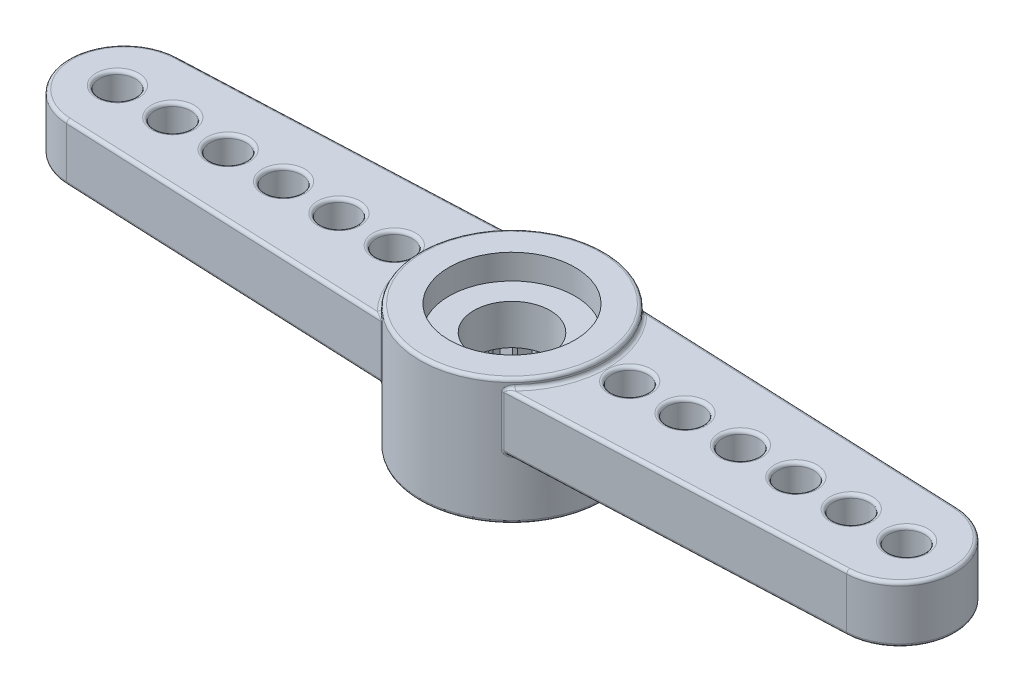
SolidWorks part; units mm, degrees
material "PETG"
ref_plane "Front Plane" through (0, 0, 0) normal (0, 0, 1) x (1, 0, 0)
ref_plane "Top Plane" through (0, 0, 0) normal (0, 1, 0) x (1, 0, 0)
ref_plane "Right Plane" through (0, 0, 0) normal (1, 0, 0) x (0, 0, -1)
ref_plane "Plane1" through (0, 2.35, 0) normal (0, 1, 0) x (1, 0, 0)
sketch "Sketch1" plane through (0, 2.35, 0) normal (0, 1, 0) x (1, 0, 0)
  line L0 (-2.1821, 2.5088) -> (-14.0857, 1.9982)
  line L1 (-14.0857, -1.9982) -> (-2.1821, -2.5088)
  arc A0 (-2.1821, -2.5088) -> (-2.1821, 2.5088) centre (0, 0) ccw
  arc A1 (-14.0857, 1.9982) -> (-14.0857, -1.9982) centre (-14, 0) ccw
extrude "Boss-Extrude1" add sketch "Sketch1" against normal blind 0.3
sketch "Sketch2" plane through (0, 2.05, 0) normal (0, -1, 0) x (1, 0, 0)
  line L0 (2.1821, 2.5088) -> (14.0857, 1.9982)
  line L1 (14.0857, -1.9982) -> (2.1821, -2.5088)
  line L2 (-2.1821, -2.5088) -> (-14.0857, -1.9982)
  line L3 (-14.0857, 1.9982) -> (-2.1821, 2.5088)
  arc A0 (14.0857, 1.9982) -> (14.0857, -1.9982) centre (14, 0) cw
  arc A1 (2.1821, -2.5088) -> (-2.1821, -2.5088) centre (0, 0) cw
  arc A2 (-14.0857, -1.9982) -> (-14.0857, 1.9982) centre (-14, 0) cw
  arc A3 (-2.1821, 2.5088) -> (2.1821, 2.5088) centre (0, 0) cw
extrude "Boss-Extrude2" add sketch "Sketch2" along normal blind 2.05
sketch "Sketch3" plane through (0, 2.35, 0) normal (0, 1, 0) x (-1, 0, 0)
  line L0 (14.0857, 1.9982) -> (2.1821, 2.5088)
  line L1 (2.1821, -2.5088) -> (14.0857, -1.9982)
  arc A0 (2.1821, 2.5088) -> (2.1821, -2.5088) centre (0, 0) cw
  arc A1 (14.0857, -1.9982) -> (14.0857, 1.9982) centre (14, 0) ccw
extrude "Cut-Extrude1" cut sketch "Sketch3" against normal blind 0.3
sketch "Sketch4" plane through (0, 0, 0) normal (0, -1, 0) x (1, 0, 0)
  circle A0 centre (0, 0) radius 3.325
extrude "Boss-Extrude3" add sketch "Sketch4" along normal blind 2.2
sketch "Sketch5" plane through (0, -2.2, 0) normal (0, -1, 0) x (1, 0, 0)
  line L0 (-2.15, -1.7146) -> (-1.4743, -1.4955)
  line L1 (-1.3811, -1.5819) -> (-1.5491, -2.2722)
  line L2 (-1.5491, -2.2722) -> (-0.968, -1.8636)
  line L3 (-0.8535, -1.9187) -> (-0.8106, -2.6278)
  line L4 (-0.8106, -2.6278) -> (-0.3757, -2.0661)
  line L5 (-0.25, -2.0851) -> (0, -2.75)
  line L6 (0, -2.75) -> (0.25, -2.0851)
  line L7 (0.3757, -2.0661) -> (0.8106, -2.6278)
  line L8 (0.8106, -2.6278) -> (0.8535, -1.9187)
  line L9 (0.968, -1.8636) -> (1.5491, -2.2722)
  line L10 (1.5491, -2.2722) -> (1.3811, -1.5819)
  line L11 (1.4743, -1.4955) -> (2.15, -1.7146)
  line L12 (2.15, -1.7146) -> (1.786, -1.1046)
  line L13 (1.8496, -0.9945) -> (2.5599, -1.0047)
  line L14 (2.5599, -1.0047) -> (2.0323, -0.529)
  line L15 (2.0606, -0.4051) -> (2.7423, -0.2055)
  line L16 (2.7423, -0.2055) -> (2.0979, 0.0935)
  line L17 (2.0884, 0.2202) -> (2.6811, 0.6119)
  line L18 (2.6811, 0.6119) -> (1.9772, 0.7077)
  line L19 (1.9307, 0.826) -> (2.3816, 1.375)
  line L20 (2.3816, 1.375) -> (1.6807, 1.259)
  line L21 (1.6015, 1.3584) -> (1.8705, 2.0159)
  line L22 (1.8705, 2.0159) -> (1.2349, 1.6985)
  line L23 (1.1299, 1.7701) -> (1.1932, 2.4777)
  line L24 (1.1932, 2.4777) -> (0.6794, 1.9871)
  line L25 (0.558, 2.0245) -> (0.4099, 2.7193)
  line L26 (0.4099, 2.7193) -> (0.0636, 2.099)
  line L27 (-0.0636, 2.099) -> (-0.4099, 2.7193)
  line L28 (-0.4099, 2.7193) -> (-0.558, 2.0245)
  line L29 (-0.6794, 1.9871) -> (-1.1932, 2.4777)
  line L30 (-1.1932, 2.4777) -> (-1.1299, 1.7701)
  line L31 (-1.2349, 1.6985) -> (-1.8705, 2.0159)
  line L32 (-1.8705, 2.0159) -> (-1.6015, 1.3584)
  line L33 (-1.6807, 1.259) -> (-2.3816, 1.375)
  line L34 (-2.3816, 1.375) -> (-1.9307, 0.826)
  line L35 (-1.9772, 0.7077) -> (-2.6811, 0.6119)
  line L36 (-2.6811, 0.6119) -> (-2.0884, 0.2202)
  line L37 (-2.0979, 0.0935) -> (-2.7423, -0.2055)
  line L38 (-2.7423, -0.2055) -> (-2.0606, -0.4051)
  line L39 (-2.0323, -0.529) -> (-2.5599, -1.0047)
  line L40 (-2.5599, -1.0047) -> (-1.8496, -0.9945)
  line L41 (-1.786, -1.1046) -> (-2.15, -1.7146)
  arc A0 (-1.4743, -1.4955) -> (-1.3811, -1.5819) centre (0, 0) ccw
  arc A1 (-0.968, -1.8636) -> (-0.8535, -1.9187) centre (0, 0) ccw
  arc A2 (-0.3757, -2.0661) -> (-0.25, -2.0851) centre (0, 0) ccw
  arc A3 (0.25, -2.0851) -> (0.3757, -2.0661) centre (0, 0) ccw
  arc A4 (0.8535, -1.9187) -> (0.968, -1.8636) centre (0, 0) ccw
  arc A5 (1.3811, -1.5819) -> (1.4743, -1.4955) centre (0, 0) ccw
  arc A6 (1.786, -1.1046) -> (1.8496, -0.9945) centre (0, 0) ccw
  arc A7 (2.0323, -0.529) -> (2.0606, -0.4051) centre (0, 0) ccw
  arc A8 (2.0979, 0.0935) -> (2.0884, 0.2202) centre (0, 0) ccw
  arc A9 (1.9772, 0.7077) -> (1.9307, 0.826) centre (0, 0) ccw
  arc A10 (1.6807, 1.259) -> (1.6015, 1.3584) centre (0, 0) ccw
  arc A11 (1.2349, 1.6985) -> (1.1299, 1.7701) centre (0, 0) ccw
  arc A12 (0.6794, 1.9871) -> (0.558, 2.0245) centre (0, 0) ccw
  arc A13 (0.0636, 2.099) -> (-0.0636, 2.099) centre (0, 0) ccw
  arc A14 (-0.558, 2.0245) -> (-0.6794, 1.9871) centre (0, 0) ccw
  arc A15 (-1.1299, 1.7701) -> (-1.2349, 1.6985) centre (0, 0) ccw
  arc A16 (-1.6015, 1.3584) -> (-1.6807, 1.259) centre (0, 0) ccw
  arc A17 (-1.9307, 0.826) -> (-1.9772, 0.7077) centre (0, 0) ccw
  arc A18 (-2.0884, 0.2202) -> (-2.0979, 0.0935) centre (0, 0) ccw
  arc A19 (-2.0606, -0.4051) -> (-2.0323, -0.529) centre (0, 0) ccw
  arc A20 (-1.8496, -0.9945) -> (-1.786, -1.1046) centre (0, 0) ccw
extrude "Cut-Extrude2" cut sketch "Sketch5" against normal blind 2.2
sketch "Sketch6" plane through (0, 0, 0) normal (0, -1, 0) x (1, 0, 0)
  line L0 (0.3365, 2.588) -> (0.4388, 2.5836)
  line L1 (0.4388, 2.5836) -> (0.4099, 2.7193)
  line L2 (0.4099, 2.7193) -> (0.3365, 2.588)
extrude "Cut-Extrude3" cut sketch "Sketch6" against normal blind 0.6
sketch "Sketch7" plane through (0, 0, 0) normal (0, -1, 0) x (1, 0, 0)
  line L0 (0.8142, -2.5675) -> (0.7655, -2.5696)
  line L1 (0.7655, -2.5696) -> (0.8106, -2.6278)
  line L2 (0.8106, -2.6278) -> (0.8142, -2.5675)
extrude "Cut-Extrude4" cut sketch "Sketch7" against normal blind 0.6
sketch "Sketch8" plane through (0, 0, 0) normal (0, -1, 0) x (1, 0, 0)
  line L0 (-1.7265, 1.944) -> (-1.8705, 2.0159)
  line L1 (-1.8705, 2.0159) -> (-1.8095, 1.867)
  arc A0 (-1.8095, 1.867) -> (-1.7265, 1.944) centre (0, 0) cw
extrude "Cut-Extrude5" cut sketch "Sketch8" against normal blind 0.6
sketch "Sketch9" plane through (0, 0, 0) normal (0, -1, 0) x (1, 0, 0)
  line L0 (-2.2228, 1.3487) -> (-2.3816, 1.375)
  line L1 (-2.3816, 1.375) -> (-2.2794, 1.2506)
  arc A0 (-2.2794, 1.2506) -> (-2.2228, 1.3487) centre (0, 0) cw
extrude "Cut-Extrude6" cut sketch "Sketch9" against normal blind 0.6
sketch "Sketch10" plane through (0, 0, 0) normal (0, -1, 0) x (1, 0, 0)
  line L0 (-2.5216, 0.6336) -> (-2.6811, 0.6119)
  line L1 (-2.6811, 0.6119) -> (-2.5468, 0.5232)
  arc A0 (-2.5468, 0.5232) -> (-2.5216, 0.6336) centre (0, 0) cw
extrude "Cut-Extrude7" cut sketch "Sketch10" against normal blind 0.6
sketch "Sketch11" plane through (0, 0, 0) normal (0, -1, 0) x (1, 0, 0)
  line L0 (-0.8203, -2.4672) -> (-0.8106, -2.6278)
  line L1 (-0.8106, -2.6278) -> (-0.7121, -2.5006)
  arc A0 (-0.7121, -2.5006) -> (-0.8203, -2.4672) centre (0, 0) cw
extrude "Cut-Extrude8" cut sketch "Sketch11" against normal blind 0.6
sketch "Sketch12" plane through (0, 0, 0) normal (0, -1, 0) x (1, 0, 0)
  line L0 (-0.3314, 2.5788) -> (-0.4099, 2.7193)
  line L1 (-0.4099, 2.7193) -> (-0.4434, 2.5619)
  arc A0 (-0.4434, 2.5619) -> (-0.3314, 2.5788) centre (0, 0) cw
extrude "Cut-Extrude9" cut sketch "Sketch12" against normal blind 0.6
sketch "Sketch13" plane through (0, 0, 0) normal (0, -1, 0) x (1, 0, 0)
  line L0 (-2.0676, -1.5764) -> (-2.15, -1.7146)
  line L1 (-2.15, -1.7146) -> (-1.997, -1.665)
  arc A0 (-1.997, -1.665) -> (-2.0676, -1.5764) centre (0, 0) cw
extrude "Cut-Extrude10" cut sketch "Sketch13" against normal blind 0.6
sketch "Sketch14" plane through (0, 0, 0) normal (0, -1, 0) x (1, 0, 0)
  line L0 (-1.5111, -2.1158) -> (-1.5491, -2.2722)
  line L1 (-1.5491, -2.2722) -> (-1.4175, -2.1796)
  arc A0 (-1.4175, -2.1796) -> (-1.5111, -2.1158) centre (0, 0) cw
extrude "Cut-Extrude11" cut sketch "Sketch14" against normal blind 0.6
sketch "Sketch15" plane through (0, 0, 0) normal (0, -1, 0) x (1, 0, 0)
  line L0 (-0.0566, -2.5994) -> (0, -2.75)
  line L1 (0, -2.75) -> (0.0566, -2.5994)
  arc A0 (0.0566, -2.5994) -> (-0.0566, -2.5994) centre (0, 0) cw
extrude "Cut-Extrude12" cut sketch "Sketch15" against normal blind 0.6
sketch "Sketch16" plane through (0, 0, 0) normal (0, -1, 0) x (1, 0, 0)
  line L0 (-2.5963, -0.1378) -> (-2.7423, -0.2055)
  line L1 (-2.7423, -0.2055) -> (-2.5879, -0.2507)
  arc A0 (-2.5879, -0.2507) -> (-2.5963, -0.1378) centre (0, 0) cw
extrude "Cut-Extrude13" cut sketch "Sketch16" against normal blind 0.6
sketch "Sketch17" plane through (0, 0, 0) normal (0, -1, 0) x (1, 0, 0)
  line L0 (-2.4404, -0.8969) -> (-2.5599, -1.0047)
  line L1 (-2.5599, -1.0047) -> (-2.399, -1.0024)
  arc A0 (-2.399, -1.0024) -> (-2.4404, -0.8969) centre (0, 0) cw
extrude "Cut-Extrude14" cut sketch "Sketch17" against normal blind 0.6
sketch "Sketch18" plane through (0, 0, 0) normal (0, -1, 0) x (1, 0, 0)
  line L0 (-1.0768, 2.3665) -> (-1.1932, 2.4777)
  line L1 (-1.1932, 2.4777) -> (-1.1789, 2.3174)
  arc A0 (-1.1789, 2.3174) -> (-1.0768, 2.3665) centre (0, 0) cw
extrude "Cut-Extrude15" cut sketch "Sketch18" against normal blind 0.6
hole_wizard "CBORE for M2.5 Hex Head Machine Screw1" positions "Sketch20" profile "Sketch19" counterbore size "M2.5" standard "ANSI Metric"
sketch "Sketch20" plane through (0, 2.35, 0) normal (0, 1, 0) x (1, 0, 0)
  point P0 (0, 0)
sketch "Sketch19" plane through (0, 2.35, 0) normal (1, 0, 0) x (0, 0, 1)
  line L0 (0, 0) -> (0, 4.55)
  line L1 (0, 4.55) -> (1.375, 4.55)
  line L3 (1.375, 4.55) -> (1.375, 0.9)
  line L4 (1.375, 0.9) -> (2.275, 0.9)
  line L5 (2.275, 0.9) -> (2.275, 0)
  line L7 (2.275, 0) -> (0, 0)
  line L11 (0, -6.35) -> (0, 107.95) construction
  dimension "Thru Hole Dia." = 2.75
  dimension "Thru Hole Depth" = 4.55
  dimension "C'Bore Dia." = 4.55
  dimension "C'Bore Depth" = 0.9
hole_wizard "Ø1.3 (1.3) Diameter Hole1" positions "Sketch22" profile "Sketch21" hole size "Ø1.3" standard "ANSI Metric"
sketch "Sketch22" plane through (0, 2.05, 0) normal (0, 1, 0) x (1, 0, 0)
  point P0 (-10.25, 0)
  point P1 (-14.25, 0)
  point P2 (4.25, 0)
  point P3 (12.25, 0)
  point P4 (10.25, 0)
  point P5 (8.25, 0)
sketch "Sketch21" plane through (-10.25, 2.05, 0) normal (1, 0, 0) x (0, 0, 1)
  line L0 (0, 0) -> (0, 4.25)
  line L1 (0, 4.25) -> (0.65, 4.25)
  line L2 (0.65, 4.25) -> (0.65, 0)
  line L5 (0.65, 0) -> (0, 0)
  line L11 (0, -6.35) -> (0, 107.95) construction
  dimension "Thru Hole Dia." = 1.3
  dimension "Thru Hole Depth" = 4.25
hole_wizard "Ø1.3 (1.3) Diameter Hole2" positions "Sketch24" profile "Sketch23" hole size "Ø1.3" standard "ANSI Metric"
sketch "Sketch24" plane through (0, 0, 0) normal (0, -1, 0) x (-1, 0, 0)
  point P0 (12.25, 0)
  point P1 (8.25, 0)
  point P2 (4.25, 0)
  point P3 (6.25, 0)
  point P4 (-14.25, 0)
  point P5 (-6.25, 0)
sketch "Sketch23" plane through (-12.25, 0, 0) normal (1, 0, 0) x (0, 0, -1)
  line L0 (0, 0) -> (0, 2.35)
  line L1 (0, 2.35) -> (0.65, 2.35)
  line L2 (0.65, 2.35) -> (0.65, 0)
  line L5 (0.65, 0) -> (0, 0)
  line L11 (0, -6.35) -> (0, 107.95) construction
  dimension "Thru Hole Dia." = 1.3
  dimension "Thru Hole Depth" = 2.35
fillet "Fillet1" radius 0.12 46 edges at (10.25, 0, 0.65) (-10.25, 0, 0.65) (6.25, 2.05, 0.65) (-3.325, 0, 0) (-2.1821, 1.025, -2.5088) (-3.325, 2.05, 0) (-2.1821, 1.025, 2.5088) (14.25, 2.05, 0.65) (-4.25, 2.05, 0.65) (-8.1339, 2.05, -2.2535) (-16, 2.05, 0) (-8.1339, 2.05, 2.2535) (-14.25, 0, 0.65) (-8.1339, 0, -2.2535) (-16, 0, 0) (-8.1339, 0, 2.2535) (14.25, 0, -0.65) (6.25, 0, -0.65) (10.25, 2.05, 0.65) (-10.25, 2.05, 0.65) (-14.25, 2.05, 0.65) (-4.25, 0, -0.65) (0, -2.2, -3.325) (4.25, 0, 0.65) (12.25, 0, 0.65) (2.1821, 1.025, -2.5088) (3.325, 0, 0) (3.325, 2.05, 0) (2.1821, 1.025, 2.5088) (8.25, 0, 0.65) (4.25, 2.05, 0.65) (12.25, 2.05, 0.65) (8.25, 2.05, 0.65) (8.1339, 0, -2.2535) (16, 0, 0) (8.1339, 0, 2.2535) (-12.25, 2.05, 0.65) (-8.25, 2.05, 0.65) (-6.25, 2.05, 0.65) (-12.25, 0, -0.65) (-8.25, 0, -0.65) (-6.25, 0, -0.65) (0, 2.35, 3.325) (8.1339, 2.05, 2.2535) (16, 2.05, 0) (8.1339, 2.05, -2.2535) tangent propagation no
